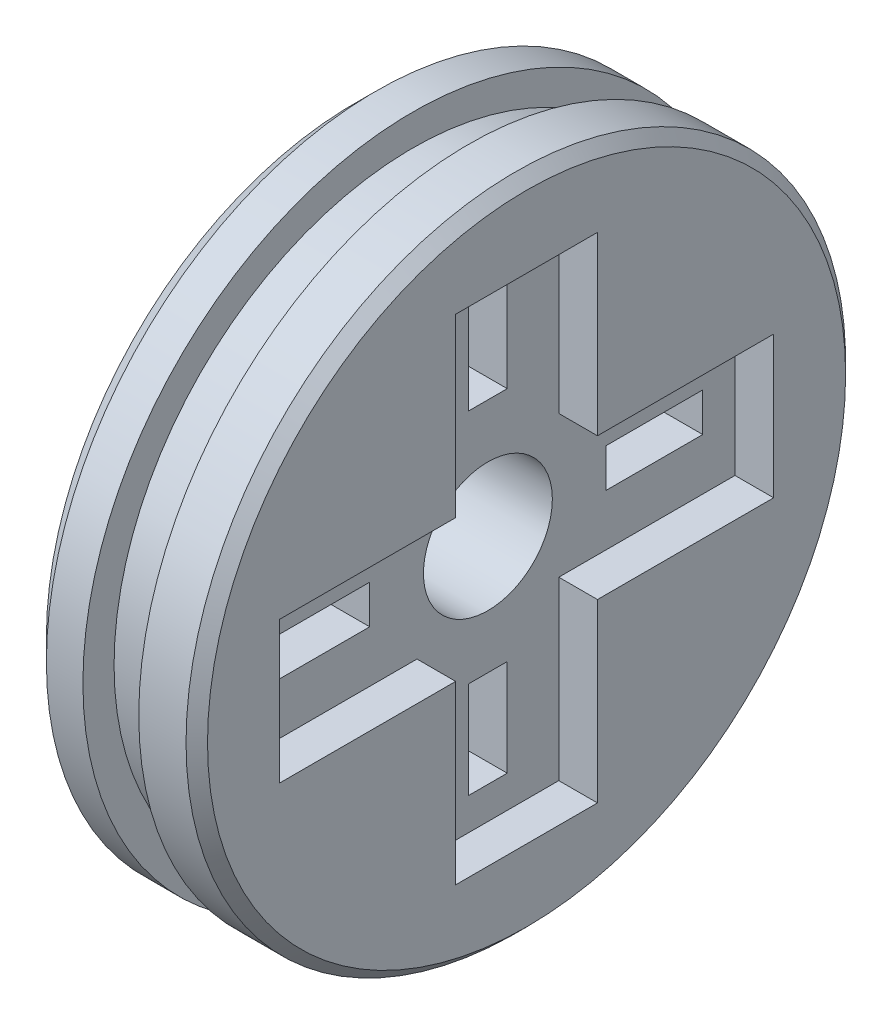
SolidWorks part; units mm, degrees
ref_plane "Front Plane" through (0, 0, 0) normal (0, 0, 1) x (1, 0, 0)
ref_plane "Top Plane" through (0, 0, 0) normal (0, 1, 0) x (1, 0, 0)
ref_plane "Right Plane" through (0, 0, 0) normal (1, 0, 0) x (0, 0, -1)
ref_plane "Plane1" through (0, 0, -52) normal (0, 0, 1) x (1, 0, 0)
sketch "Sketch1" plane through (0, 0, -52) normal (0, 0, 1) x (1, 0, 0)
  line L0 (-90.2, -65) -> (-72.2, -65) construction
  line L1 (-77.2, -65) -> (-85.2, -65)
  line L2 (-85.2, -65) -> (-85.2, -50.65)
  line L3 (-85.2, -50.65) -> (-84.2, -49.65)
  line L4 (-84.2, -49.65) -> (-77.7, -49.65)
  line L5 (-77.7, -49.65) -> (-77.2, -50.15)
  line L6 (-77.2, -50.15) -> (-77.2, -65)
revolve "Revolve1" add sketch "Sketch1" angle 360 about L0
sketch "Sketch2" plane through (0, 0, -52) normal (0, 0, 1) x (1, 0, 0)
  line L0 (-87.5, -65) -> (-74.9, -65) construction
  line L1 (-79.9, -51.1) -> (-82.5, -51.1)
  line L2 (-82.5, -51.1) -> (-82.5, -48.65)
  line L3 (-82.5, -48.65) -> (-79.9, -48.65)
  line L4 (-79.9, -48.65) -> (-79.9, -51.1)
revolve "Revolve2" add sketch "Sketch2" angle 360 about L0
combine bodies "Combine1" operation type subtract main body 101 bodies to subtract 102
sketch "Sketch3" plane through (0, 0, 0) normal (0, 0, 1) x (1, 0, 0)
  line L1 (-79, -76.5) -> (-76.7, -76.5)
  line L2 (-79, -76.5) -> (-79, -53.5)
  line L3 (-79, -53.5) -> (-76.7, -53.5)
  line L4 (-76.7, -76.5) -> (-76.7, -53.5)
extrude "Boss-Extrude1" add sketch "Sketch3" along normal blind 6.6 from offset 55.3 separate body offset against normal yes
combine bodies "Combine2" operation type subtract main body 103 bodies to subtract 104
sketch "Sketch4" plane through (0, 0, 0) normal (0, 0, 1) x (1, 0, 0)
  line L1 (-79, -68.3) -> (-76.7, -68.3)
  line L2 (-79, -68.3) -> (-79, -61.7)
  line L3 (-79, -61.7) -> (-76.7, -61.7)
  line L4 (-76.7, -68.3) -> (-76.7, -61.7)
extrude "Boss-Extrude2" add sketch "Sketch4" along normal blind 23 from offset 63.5 separate body offset against normal yes
combine bodies "Combine3" operation type subtract main body 105 bodies to subtract 106
sketch "Sketch5" plane through (0, 0, 0) normal (1, 0, 0) x (0, 0, -1)
  circle A0 centre (52, -65) radius 4.6
extrude "Boss-Extrude3" add sketch "Sketch5" along normal blind 2.3 from offset 79 separate body offset against normal yes
combine bodies "Combine4" operation type subtract main body 107 bodies to subtract 108
sketch "Sketch6" plane through (0, 0, 0) normal (1, 0, 0) x (0, 0, -1)
  circle A0 centre (52, -65) radius 7.1
extrude "Boss-Extrude4" add sketch "Sketch6" along normal blind 1.7 from offset 85.7 separate body offset against normal yes
combine bodies "Combine5" operation type subtract main body 109 bodies to subtract 110
sketch "Sketch7" plane through (0, 0, 0) normal (1, 0, 0) x (0, 0, -1)
  circle A0 centre (52, -65) radius 3
extrude "Boss-Extrude5" add sketch "Sketch7" along normal blind 5.2 from offset 84.1 separate body offset against normal yes
combine bodies "Combine6" operation type subtract main body 111 bodies to subtract 112
sketch "Sketch8" plane through (0, 0, 0) normal (0, 0, 1) x (1, 0, 0)
  line L1 (-83, -59.5) -> (-78.9, -59.5)
  line L2 (-83, -59.5) -> (-83, -57.4)
  line L3 (-83, -57.4) -> (-78.9, -57.4)
  line L4 (-78.9, -59.5) -> (-78.9, -57.4)
extrude "Boss-Extrude6" add sketch "Sketch8" along normal blind 1.8 from offset 52.9 separate body offset against normal yes
combine bodies "Combine7" operation type subtract main body 113 bodies to subtract 114
sketch "Sketch9" plane through (0, 0, 0) normal (0, 0, 1) x (1, 0, 0)
  line L1 (-83, -65.9) -> (-78.9, -65.9)
  line L2 (-83, -65.9) -> (-83, -64.1)
  line L3 (-83, -64.1) -> (-78.9, -64.1)
  line L4 (-78.9, -65.9) -> (-78.9, -64.1)
extrude "Boss-Extrude7" add sketch "Sketch9" along normal blind 2.1 from offset 46.5 separate body offset against normal yes
combine bodies "Combine8" operation type subtract main body 115 bodies to subtract 116
sketch "Sketch10" plane through (0, 0, 0) normal (0, 0, 1) x (1, 0, 0)
  line L1 (-83, -72.6) -> (-78.9, -72.6)
  line L2 (-83, -72.6) -> (-83, -70.5)
  line L3 (-83, -70.5) -> (-78.9, -70.5)
  line L4 (-78.9, -72.6) -> (-78.9, -70.5)
extrude "Boss-Extrude8" add sketch "Sketch10" along normal blind 1.8 from offset 52.9 separate body offset against normal yes
combine bodies "Combine9" operation type subtract main body 117 bodies to subtract 118
sketch "Sketch11" plane through (0, 0, 0) normal (0, 0, 1) x (1, 0, 0)
  line L1 (-83, -65.9) -> (-78.9, -65.9)
  line L2 (-83, -65.9) -> (-83, -64.1)
  line L3 (-83, -64.1) -> (-78.9, -64.1)
  line L4 (-78.9, -65.9) -> (-78.9, -64.1)
extrude "Boss-Extrude9" add sketch "Sketch11" along normal blind 2.1 from offset 59.6 separate body offset against normal yes
combine bodies "Combine10" operation type subtract main body 119 bodies to subtract 120
sketch "Sketch12" plane through (0, 0, 0) normal (0, 0, 1) x (1, 0, 0)
  line L1 (-84.2, -57.4) -> (-78.9, -57.4)
  line L2 (-84.2, -57.4) -> (-84.2, -55)
  line L3 (-84.2, -55) -> (-78.9, -55)
  line L4 (-78.9, -57.4) -> (-78.9, -55)
extrude "Boss-Extrude10" add sketch "Sketch12" along normal blind 1.8 from offset 52.9 separate body offset against normal yes
combine bodies "Combine11" operation type subtract main body 121 bodies to subtract 122
sketch "Sketch13" plane through (0, 0, 0) normal (0, 0, 1) x (1, 0, 0)
  line L1 (-84.2, -65.9) -> (-78.9, -65.9)
  line L2 (-84.2, -65.9) -> (-84.2, -64.1)
  line L3 (-84.2, -64.1) -> (-78.9, -64.1)
  line L4 (-78.9, -65.9) -> (-78.9, -64.1)
extrude "Boss-Extrude11" add sketch "Sketch13" along normal blind 2.4 from offset 44.4 separate body offset against normal yes
combine bodies "Combine12" operation type subtract main body 123 bodies to subtract 124
sketch "Sketch14" plane through (0, 0, 0) normal (0, 0, 1) x (1, 0, 0)
  line L1 (-84.2, -75) -> (-78.9, -75)
  line L2 (-84.2, -75) -> (-84.2, -72.6)
  line L3 (-84.2, -72.6) -> (-78.9, -72.6)
  line L4 (-78.9, -75) -> (-78.9, -72.6)
extrude "Boss-Extrude12" add sketch "Sketch14" along normal blind 1.8 from offset 52.9 separate body offset against normal yes
combine bodies "Combine13" operation type subtract main body 125 bodies to subtract 126
sketch "Sketch15" plane through (0, 0, 0) normal (0, 0, 1) x (1, 0, 0)
  line L1 (-84.2, -65.9) -> (-78.9, -65.9)
  line L2 (-84.2, -65.9) -> (-84.2, -64.1)
  line L3 (-84.2, -64.1) -> (-78.9, -64.1)
  line L4 (-78.9, -65.9) -> (-78.9, -64.1)
extrude "Boss-Extrude13" add sketch "Sketch15" along normal blind 2.4 from offset 62 separate body offset against normal yes
combine bodies "Combine14" operation type subtract main body 127 bodies to subtract 128
